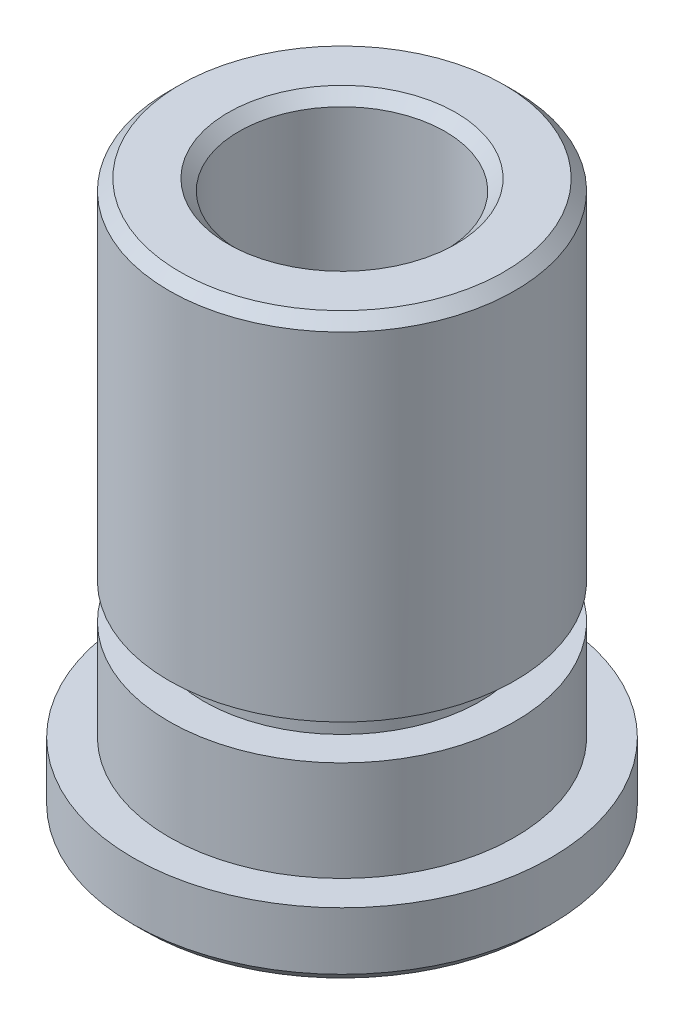
SolidWorks part; units mm, degrees
material "Aluminum Bronze"
ref_plane "Front" through (0, 0, 0) normal (0, 0, 1) x (1, 0, 0)
ref_plane "Top" through (0, 0, 0) normal (0, 1, 0) x (1, 0, 0)
ref_plane "Right" through (0, 0, 0) normal (1, 0, 0) x (0, 0, -1)
ref_axis "side-side" through (80.9, 0, 0) along (-1, 0, 0)
ref_axis "up-down" through (0, 50, 0) along (0, -1, 0)
ref_axis "front-back" through (0, 0, -80.9) along (0, 0, 1)
sketch "Sketch2" plane through (0, 0, 0) normal (1, 0, 0) x (0, 0, -1)
  line L0 (0, -1.3599) -> (0, -6.0041) construction
  line L1 (50, 0) -> (-50, 0) construction
  line L2 (2.3685, 12.7) -> (3.9751, 12.7)
  line L3 (2.3685, 12.7) -> (2.3685, 0)
  line L4 (2.3685, 0) -> (4.8006, 0)
  line L5 (4.8006, 1.5748) -> (4.8006, 0)
  line L6 (3.9751, 3.8748) -> (3.9751, 1.5748)
  line L7 (3.9751, 4.6876) -> (3.175, 4.6876)
  line L8 (4.8006, 1.5748) -> (3.9751, 1.5748)
  line L9 (3.9751, 12.7) -> (3.9751, 4.6876)
  line L11 (3.9751, 3.8748) -> (3.175, 3.8748)
  line L12 (3.175, 4.6876) -> (3.175, 3.8748)
  dimension "D1" = 4.7371
  dimension "D2" = 7.9502
  dimension "D3" = 1.5748
  dimension "D4" = 9.6012
  dimension "D5" = 12.7
  dimension "D6" = 0.8128
  dimension "D7" = 6.35
  dimension "D8" = 2.3
revolve "Revolve1" add sketch "Sketch2" angle 360 about L0
chamfer "Chamfer1" distance 0.25 angle 45 4 edges at (0, 12.7, 2.3685) (0, 0, 4.8006) (0, 12.7, 3.9751) (0, 0, 2.3685)
